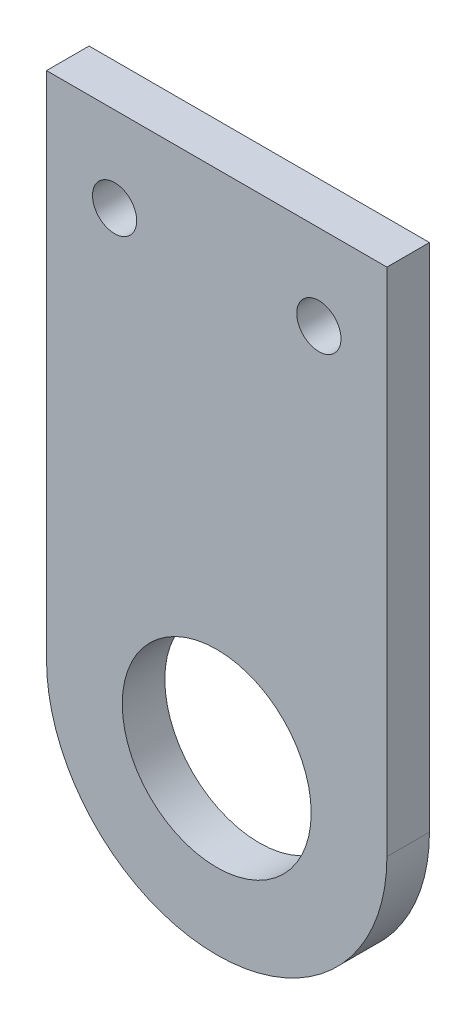
SolidWorks part; units mm, degrees
material "6061 合金"
ref_plane "前视基准面" through (0, 0, 0) normal (0, 0, 1) x (1, 0, 0)
ref_plane "上视基准面" through (0, 0, 0) normal (0, 1, 0) x (1, 0, 0)
ref_plane "右视基准面" through (0, 0, 0) normal (1, 0, 0) x (0, 0, -1)
other "Configuration Table"
sketch "草图1" plane through (0, 0, 0) normal (0, 0, 1) x (1, 0, 0)
  circle A0 centre (0, 0) radius 20
  circle A1 centre (0, 0) radius 11
  dimension "D1" = 40
  dimension "D2" = 22
extrude "凸台-拉伸1" add sketch "草图1" along normal blind 60 contours A1 | A0 region at (0, 0, 0)
ref_plane "基准面1" through (0, 0, 30) normal (0, 0, 1) x (1, 0, 0)
sketch "草图2" plane through (0, 0, 30) normal (0, 0, 1) x (1, 0, 0)
  line L0 (0, 0) -> (-70, -70) construction
  line L1 (-70, -70) -> (-70, -320) construction
  line L2 (0, -57.3148) -> (0, 49.9409) construction
  line L3 (-56.8582, 0) -> (46.4003, 0) construction
  line L4 (-14.1421, 14.1421) -> (-90, -61.7157)
  line L5 (14.1421, -14.1421) -> (-50, -78.2843)
  line L6 (-90, -61.7157) -> (-90, -320)
  line L7 (-50, -78.2843) -> (-50, -320)
  line L8 (-90, -320) -> (-50, -320)
  circle A2 centre (0, 0) radius 20 construction
  arc A3 (-14.1421, 14.1421) -> (14.1421, -14.1421) centre (0, 0) ccw
  dimension "D1" = 45
  dimension "D2" = 250
  dimension "D3" = 70
  dimension "D4" = 40
  dimension "D5" = 40
extrude "凸台-拉伸2" add sketch "草图2" along normal mid plane 60 contours L7 L8 L6 L4 A3 L5
sketch "草图4" plane through (0, 0, 60) normal (0, 0, 1) x (1, 0, 0)
  line L0 (-90, -61.7157) -> (-90, -320) construction
  line L1 (-90, -290) -> (-50, -290)
  line L2 (-90, -290) -> (-90, -350)
  line L4 (-50, -290) -> (-50, -350)
  line L5 (-50, -78.2843) -> (-50, -320) construction
  line L6 (-90, -320) -> (-50, -320) construction
  arc A0 (-90, -350) -> (-50, -350) centre (-70, -350) ccw
  circle A1 centre (-70, -350) radius 11.1
  dimension "D3" = 22.2
  dimension "D1" = 30
  dimension "D2" = 30
extrude "凸台-拉伸3" add sketch "草图4" along normal blind 5
mirror "镜向1" about plane through (0, 0, 30) normal (0, 0, 1) of "凸台-拉伸3"
sketch "草图5" plane through (0, 0, 0) normal (0, 1, 0) x (1, 0, 0)
  line L0 (0, 0) -> (0, -78.0582) construction
ref_plane "基准面2" through (-70, 0, 0) normal (-1, 0, 0) x (0, 0, 1)
sketch "草图7" plane through (-70, 0, 0) normal (-1, 0, 0) x (0, 0, 1)
  line L0 (-34.1239, -350) -> (109.535, -350) construction
sketch "草图8" plane through (0, 0, 60) normal (0, 0, 1) x (1, 0, 0)
  line L0 (0, 0) -> (-70, -70) construction
  circle A0 centre (-35.3553, -35.3553) radius 11
  dimension "D1" = 22
  dimension "D2" = 50
extrude "切除-拉伸1" cut sketch "草图8" against normal blind 100
fillet "圆角4" radius 20 2 edges at (-90, -61.7157, 30) (-50, -78.2843, 30)
fillet "圆角1" [suppressed] radius 50
fillet "圆角2" [suppressed] radius 3
sketch "草图9" plane through (0, 0, 65) normal (0, 0, 1) x (1, 0, 0)
  circle A0 centre (-70, -350) radius 13
  dimension "D1" = 26
extrude "切除-拉伸2" [suppressed] cut sketch "草图9" against normal blind 0.75
sketch "草图10" plane through (0, 0, -5) normal (0, 0, -1) x (-1, 0, 0)
  circle A0 centre (70, -350) radius 13
  dimension "D1" = 26
extrude "切除-拉伸3" [suppressed] cut sketch "草图10" against normal blind 0.75 contours A0
sketch "草图11" plane through (-90, 0, 0) normal (-1, 0, 0) x (0, 0, 1)
  circle A0 centre (48.5, -118.9949) radius 2.75
  circle A1 centre (48.5, -183.9949) radius 2.75
  circle A2 centre (48.5, -248.9949) radius 2.75
  circle A3 centre (11.5, -248.9949) radius 2.75
  circle A4 centre (11.5, -183.9949) radius 2.75
  circle A5 centre (11.5, -118.9949) radius 2.75
  dimension "D1" = 5.5
extrude "切除-拉伸4" [suppressed] cut sketch "草图11" against normal through all contours A1 | A2 | A0 | A3 | A4 | A5
sketch "草图12" [suppressed] plane through (-90, 0, 0) normal (-1, 0, 0) x (0, 0, 1)
  line L0 (30, -62.0134) -> (30, -339.6946) construction
  line L1 (10, -128.9949) -> (50, -128.9949)
  line L2 (10, -128.9949) -> (10, -173.9949)
  line L3 (10, -173.9949) -> (50, -173.9949)
  line L4 (50, -128.9949) -> (50, -173.9949)
  line L5 (10, -193.9949) -> (50, -193.9949)
  line L6 (10, -193.9949) -> (10, -238.9949)
  line L7 (10, -238.9949) -> (50, -238.9949)
  line L8 (50, -193.9949) -> (50, -238.9949)
  line L9 (10, -258.9949) -> (50, -258.9949)
  line L10 (10, -258.9949) -> (10, -290)
  line L11 (10, -290) -> (50, -290)
  line L12 (50, -258.9949) -> (50, -290)
  line L13 (19.5, -173.9949) -> (40.5, -173.9949)
  line L14 (19.5, -173.9949) -> (19.5, -193.9949)
  line L15 (19.5, -193.9949) -> (40.5, -193.9949)
  line L16 (40.5, -173.9949) -> (40.5, -193.9949)
  line L17 (19.5, -238.9949) -> (40.5, -238.9949)
  line L18 (19.5, -238.9949) -> (19.5, -258.9949)
  line L19 (19.5, -258.9949) -> (40.5, -258.9949)
  line L20 (40.5, -238.9949) -> (40.5, -258.9949)
  line L21 (60, -82.4264) -> (60, -290) construction
  line L22 (0, -290) -> (0, -82.4264) construction
  line L23 (57, -320) -> (3, -320) construction
  circle A0 centre (48.5, -118.9949) radius 2.75 construction
  circle A1 centre (48.5, -183.9949) radius 2.75 construction
  circle A2 centre (48.5, -248.9949) radius 2.75 construction
  dimension "D1" = 10
  dimension "D2" = 10
  dimension "D3" = 10
  dimension "D4" = 8
  dimension "D5" = 10
  dimension "D6" = 10
  dimension "D7" = 10
  dimension "D8" = 30
extrude "减重" [suppressed] cut sketch "草图12" against normal through all contours L0 L1 L2 L3 | L15 L0 L17 L7 L8 L5 | L0 L5 L6 L7 | L19 L0 L11 L12 L9 | L0 L9 L10 L11 | L1 L0 L13 L3 L4
fillet "圆角3" [suppressed] radius 3
sketch "草图13" plane through (0, 0, 60) normal (0, 0, 1) x (1, 0, 0)
  circle A0 centre (0, 0) radius 13
  circle A1 centre (-35.3553, -35.3553) radius 13
  dimension "D1" = 26
  dimension "D2" = 26
extrude "切除-拉伸6" [suppressed] cut sketch "草图13" against normal blind 1.75
sketch "草图14" plane through (0, 0, 0) normal (0, 0, -1) x (-1, 0, 0)
  circle A0 centre (0, 0) radius 13
  circle A1 centre (35.3553, -35.3553) radius 13
  dimension "D1" = 26
  dimension "D2" = 26
extrude "切除-拉伸7" [suppressed] cut sketch "草图14" against normal blind 1.75
sketch "草图15" [suppressed] plane through (0, 0, 0) normal (0, 0, -1) x (-1, 0, 0)
  line L0 (0, 0) -> (70, -350) construction
  line L1 (56.2719, -67.2005) -> (60.1942, -86.8121) construction
  line L2 (70, -350) -> (204.3541, -323.1292) construction
  circle A0 centre (56.2719, -67.2005) radius 2.75
  circle A1 centre (75.2172, -73.6095) radius 2.75
  circle A2 centre (60.1942, -86.8121) radius 2.75
  dimension "D1" = 5.5
  dimension "D2" = 20
  dimension "D3" = 20
  dimension "D4" = 20
  dimension "D5" = 42
  dimension "D6" = 270
extrude "切除-拉伸8" [suppressed] cut sketch "草图15" against normal through all contours A2 | A0 | A1
ref_plane "小腿主干连杆面" through (0, 0, 0) normal (0.9806, -0.1961, 0) x (0, 0, -1)
ref_plane "小腿主干对称面" through (0, 0, 30) normal (0, 0, -1) x (-1, 0, 0)
sketch "草图16" plane through (0, 0, 60) normal (0, 0, 1) x (1, 0, 0)
  line L0 (0, 0) -> (-70, -350)
  line L1 (-35.3553, -35.3553) -> (0, 0)
sketch "草图17" plane through (0, 0, 60) normal (0, 0, 1) x (1, 0, 0)
  line L0 (0, 0) -> (-70, -350) construction
  line L1 (118.6974, 32.5948) -> (32.9122, -396.3312) construction
  line L2 (92.7764, -97.0102) -> (20.2919, -82.5133)
  line L3 (73.1648, -195.0683) -> (0.6803, -180.5713)
  circle A0 centre (20.2919, -82.5133) radius 46
  circle A1 centre (0.6803, -180.5713) radius 46
  dimension "D3" = 92
  dimension "D4" = 92
  dimension "D1" = 110
  dimension "D2" = 73.92
  dimension "D5" = 180
  dimension "D6" = 280
sketch "草图18" plane through (0, 0, 60) normal (0, 0, 1) x (1, 0, 0)
  line L1 (14.1421, -14.1421) -> (-44.1421, -72.4264) construction
  line L3 (14.1421, -14.1421) -> (-44.1421, -72.4264)
  line L4 (15.4873, -12.6548) -> (52.8188, -49.9864)
  line L5 (-50, -128.5133) -> (20.2919, -128.5133)
  line L10 (-90, -290) -> (-50, -290)
  line L11 (-50, -290) -> (-50, -86.5685)
  line L12 (-44.1421, -72.4264) -> (14.1421, -14.1421)
  line L13 (-14.1421, 14.1421) -> (-84.1421, -55.8579)
  line L14 (-90, -70) -> (-90, -290)
  line L16 (-50, -128.5133) -> (-50, -86.5685)
  line L17 (-44.1421, -72.4264) -> (14.1421, -14.1421)
  circle A0 centre (20.2919, -82.5133) radius 46 construction
  arc A1 (14.1421, -14.1421) -> (-14.1421, 14.1421) centre (0, 0) ccw construction
  arc A2 (14.1421, -14.1421) -> (-14.1421, 14.1421) centre (0, 0) ccw
  arc A3 (14.1421, -14.1421) -> (15.4873, -12.6548) centre (0, 0) ccw
  arc A4 (20.2919, -128.5133) -> (52.8188, -49.9864) centre (20.2919, -82.5133) ccw
  circle A5 centre (20.2919, -82.5133) radius 35
  arc A9 (-84.1421, -55.8579) -> (-90, -70) centre (-70, -70) ccw
  arc A10 (-84.1421, -55.8579) -> (-90, -70) centre (-70, -70) ccw
  arc A11 (-44.1421, -72.4264) -> (-50, -86.5685) centre (-30, -86.5685) ccw
  arc A12 (-44.1421, -72.4264) -> (-50, -86.5685) centre (-30, -86.5685) ccw
  line M14 (-50, -290) -> (-50, -86.5685)
  line M15 (-44.1421, -72.4264) -> (14.1421, -14.1421)
  arc M16 (14.1421, -14.1421) -> (-14.1421, 14.1421) centre (0, 0) ccw
  arc M22 (-50, -86.5685) -> (-44.1421, -72.4264) centre (-30, -86.5685) cw
  dimension "D2" = 70
  dimension "D1" = 0
extrude "凸台-拉伸4" add sketch "草图18" against normal blind 5 from offset 25 contours L5 A4 L4 A5 M16 M15 M22 M14 region at (16.0508, -14.5165, 60) offset against normal yes
sketch "草图19" plane through (0, 0, 0) normal (0, 0, -1) x (-1, 0, 0)
  line L0 (50, -86.5685) -> (50, -290) construction
  line L1 (50, -134.5713) -> (50, -226.5713)
  line L2 (-0.6803, -134.5713) -> (50, -134.5713)
  line L3 (-0.6803, -226.5713) -> (50, -226.5713)
  circle A0 centre (-0.6803, -180.5713) radius 46 construction
  arc A1 (-0.6803, -134.5713) -> (-0.6803, -226.5713) centre (-0.6803, -180.5713) ccw
  circle A2 centre (-0.6803, -180.5713) radius 35
  dimension "D1" = 70
extrude "凸台-拉伸5" add sketch "草图19" against normal blind 5 from offset 25 offset against normal yes
fillet "圆角5" radius 10 2 edges at (-50, -226.5713, 27.5) (-50, -128.5133, 32.5)
sketch "草图21" plane through (0, 0, 65) normal (0, 0, 1) x (1, 0, 0)
  line L0 (-70, -350) -> (-70, -6.9331) construction
  circle A0 centre (-70, -75) radius 2.6
  circle A1 centre (-70, -250) radius 2.6
  circle A2 centre (-58, -300) radius 2.6
  circle A3 centre (-82, -300) radius 2.6
  dimension "D1" = 5.2
  dimension "D2" = 12
  dimension "D3" = 50
  dimension "D4" = 100
  dimension "D5" = 175
extrude "切除-拉伸9" cut sketch "草图21" against normal through all both and the other way through all
sketch "草图22" plane through (-90, 0, 0) normal (-1, 0, 0) x (0, 0, 1)
  line L1 (-5, -370) -> (60, -370)
  line L2 (-5, -370) -> (-5, 20)
  line L3 (-5, 20) -> (60, 20)
  line L4 (60, -370) -> (60, 20)
extrude "切除-拉伸10" cut sketch "草图22" against normal through all both contours L2 L3 L4 L1
